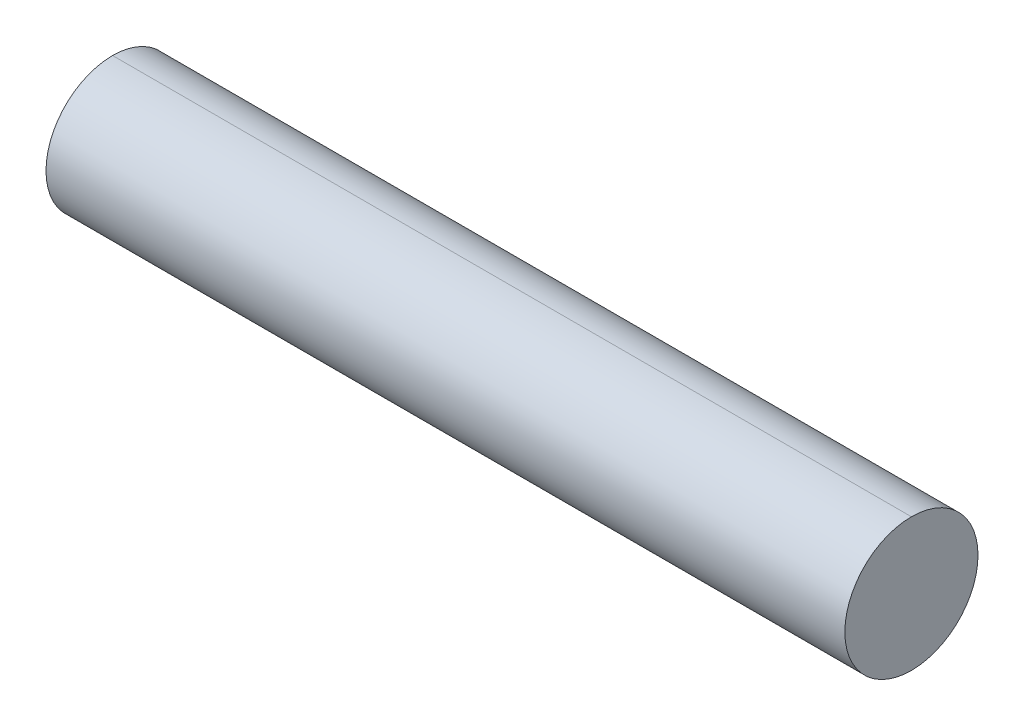
SolidWorks part; units mm, degrees
material "AISI 4340 Steel, normalized"
ref_plane "Front Plane" through (0, 0, 0) normal (0, 0, 1) x (1, 0, 0)
ref_plane "Top Plane" through (0, 0, 0) normal (0, 1, 0) x (1, 0, 0)
ref_plane "Right Plane" through (0, 0, 0) normal (1, 0, 0) x (0, 0, -1)
sketch "Sketch1" plane through (0, 0, 0) normal (1, 0, 0) x (0, 0, -1)
  circle A0 centre (0, 0) radius 19.05
  dimension "D1" = 38.1
extrude "Boss-Extrude1" add sketch "Sketch1" along normal blind 228.6
split line "Split Line1"
